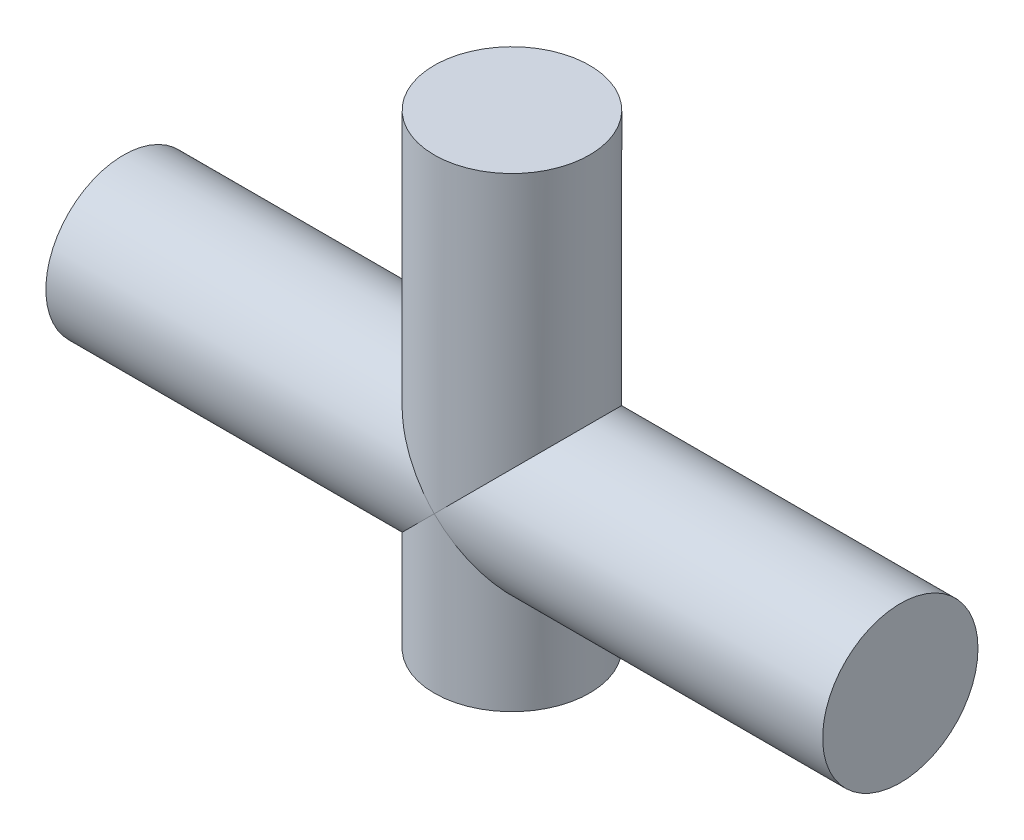
SolidWorks part; units mm, degrees
ref_plane "Front Plane" through (0, 0, 0) normal (0, 0, 1) x (1, 0, 0)
ref_plane "Top Plane" through (0, 0, 0) normal (0, 1, 0) x (1, 0, 0)
ref_plane "Right Plane" through (0, 0, 0) normal (1, 0, 0) x (0, 0, -1)
sketch "Sketch1" plane through (0, 0, 0) normal (0, 1, 0) x (1, 0, 0)
  circle A0 centre (0, 0) radius 6.35
  dimension "D1" = 12.7
sketch "Sketch2" plane through (0, 0, 0) normal (1, 0, 0) x (0, 0, -1)
  circle A0 centre (0, 0) radius 6.35
  dimension "D1" = 12.7
extrude "Boss-Extrude1" add sketch "Sketch2" along normal blind 31.75 and the other way blind 31.75
extrude "Boss-Extrude2" add sketch "Sketch1" along normal blind 25.4 and the other way blind 12.7
